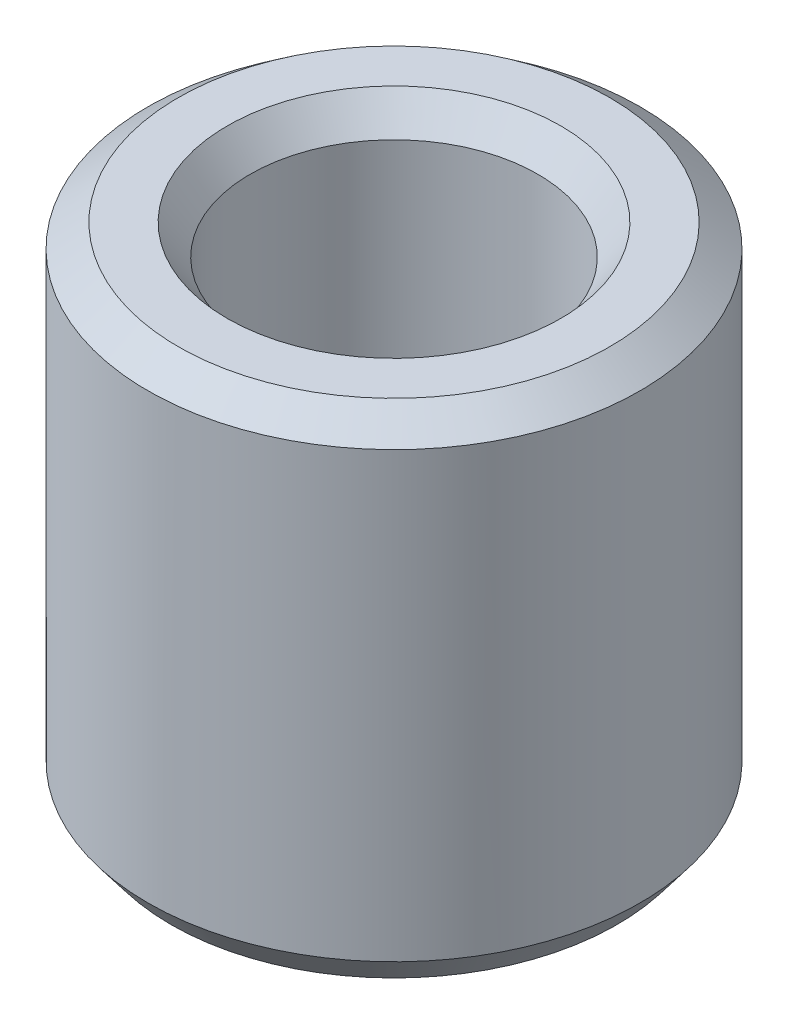
SolidWorks part; units mm, degrees
ref_plane "Front Plane" through (0, 0, 0) normal (0, 0, 1) x (1, 0, 0)
ref_plane "Top Plane" through (0, 0, 0) normal (0, 1, 0) x (1, 0, 0)
ref_plane "Right Plane" through (0, 0, 0) normal (1, 0, 0) x (0, 0, -1)
sketch "Sketch1" plane through (0, 0, 0) normal (0, 1, 0) x (1, 0, 0)
  circle A0 centre (0, 0) radius 20
  dimension "SLEEVE_OD" = 40
extrude "Boss-Extrude1" add sketch "Sketch1" along normal blind 40.3829
sketch "Sketch2" plane through (0, 0, 0) normal (0, 1, 0) x (1, 0, 0)
  circle A0 centre (0, 0) radius 11.6866
  dimension "BORE_D" = 23.3732
extrude "Cut-Extrude1" cut sketch "Sketch2" along normal through all
chamfer "Chamfer1" distance 1.8715 angle 52.773 4 edges at (0, 40.3829, 11.6866) (0, 0, 11.6866) (0, 0, 20) (0, 40.3829, 20) first distance on face at (0, 40.3829, 11.6866) first distance on face at (0, 0, 11.6866) first distance on face at (0, 40.3829, 20)
